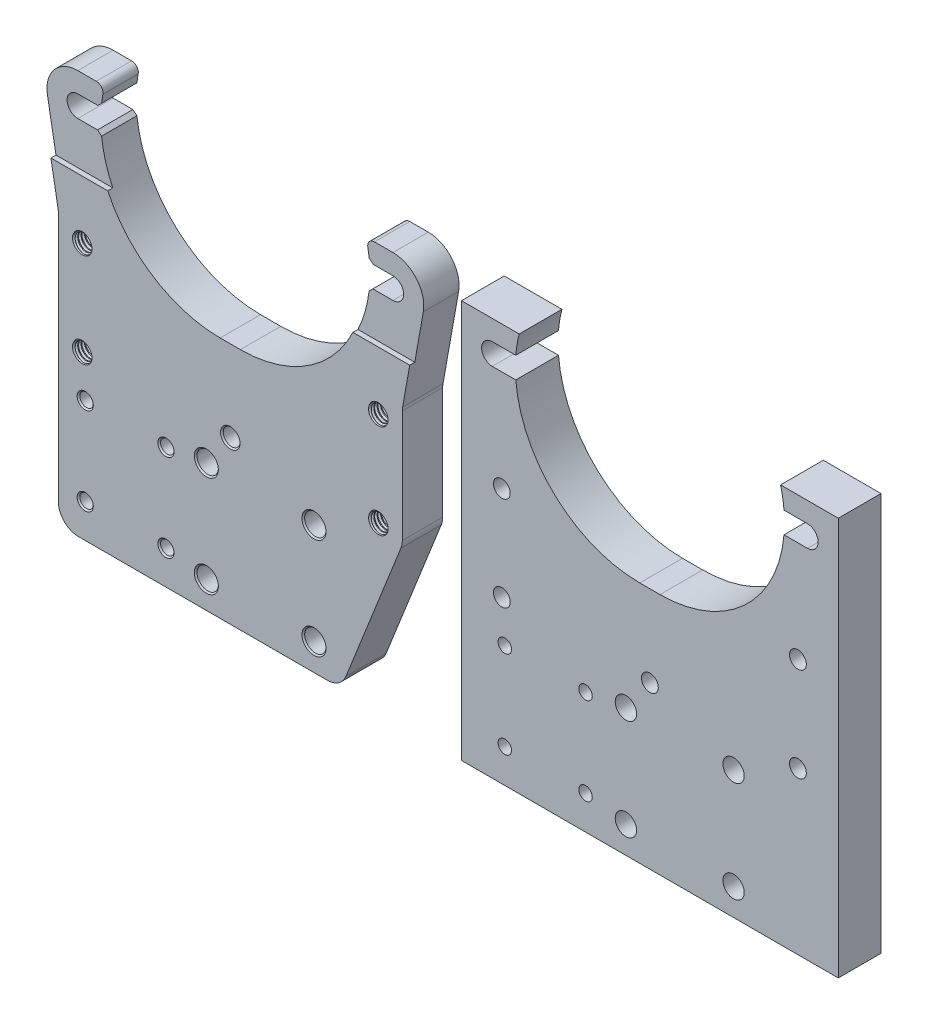
SolidWorks part; units mm, degrees
ref_plane "Front Plane" through (0, 0, 0) normal (0, 0, 1) x (1, 0, 0)
ref_plane "Top Plane" through (0, 0, 0) normal (0, 1, 0) x (1, 0, 0)
ref_plane "Right Plane" through (0, 0, 0) normal (1, 0, 0) x (0, 0, -1)
sketch "Sketch1" plane through (0, 0, 0) normal (0, 0, 1) x (1, 0, 0)
  line L0 (-8, 7.5) -> (8, 7.5) construction
  line L5 (-26, 6.5) -> (-14, 6.5) construction
  line L7 (-8, -7.5) -> (8, -7.5) construction
  line L8 (-8, -7.5) -> (-8, 7.5) construction
  line L9 (-8, 7.5) -> (8, 7.5) construction
  line L10 (8, -7.5) -> (8, 7.5) construction
  line L11 (-8, -7.5) -> (8, 7.5) construction
  line L12 (-8, 7.5) -> (8, -7.5) construction
  line L13 (-8, 7.5) -> (-8, -7.5) construction
  line L14 (-26, -6.5) -> (-14, -6.5) construction
  line L15 (-26, -6.5) -> (-26, 6.5) construction
  line L16 (-26, 6.5) -> (-14, 6.5) construction
  line L17 (-14, -6.5) -> (-14, 6.5) construction
  line L18 (-26, -6.5) -> (-14, 6.5) construction
  line L19 (-26, 6.5) -> (-14, -6.5) construction
  line L20 (0, 0) -> (-20, 0) construction
  line L21 (-6.4375, 59.6343) -> (-6.4375, -58.2445) construction
  line L22 (-30, -11.5) -> (12, -11.5)
  line L23 (-30, -11.5) -> (-30, 11.5)
  line L24 (-30, 11.5) -> (12, 11.5)
  line L25 (12, -11.5) -> (12, 11.5)
  line L26 (-30, -11.5) -> (12, 11.5) construction
  line L27 (-30, 11.5) -> (12, -11.5) construction
  line L28 (-11.5, -15) -> (-28.5, -15) construction
  line L29 (-11.5, -15) -> (-11.5, 15) construction
  line L30 (-11.5, 15) -> (-28.5, 15) construction
  line L31 (-28.5, -15) -> (-28.5, 15) construction
  line L32 (-11.5, -15) -> (-28.5, 15) construction
  line L33 (-11.5, 15) -> (-28.5, -15) construction
  line L34 (-59, 15) -> (41, 15) construction
  line L35 (-59, 15) -> (-59, 24) construction
  line L36 (-59, 24) -> (41, 24) construction
  line L37 (41, 15) -> (41, 24) construction
  line L38 (-59, -10) -> (41, -10) construction
  line L39 (-59, -10) -> (-59, 10) construction
  line L40 (-59, 10) -> (41, 10) construction
  line L41 (41, -10) -> (41, 10) construction
  line L42 (-59, -10) -> (41, 10) construction
  line L43 (-59, 10) -> (41, -10) construction
  line L44 (-30, -11.5) -> (12, -11.5)
  line L45 (-30, -11.5) -> (-30, 29)
  line L46 (-30, 29) -> (12, 29)
  line L47 (12, -11.5) -> (12, 29)
  line L48 (-4.4375, 43.1) -> (17.4825, 43.1) construction
  line L49 (-4.4375, 43.1) -> (-26.3575, 43.1) construction
  line L50 (-24.8575, 43.1) -> (-27.8575, 43.1) construction
  line L51 (-24.8575, 41.5125) -> (-27.8575, 41.5125)
  line L52 (-24.8575, 44.6875) -> (-27.8575, 44.6875)
  line L53 (15.9825, 43.1) -> (18.9825, 43.1) construction
  line L54 (15.9825, 44.6875) -> (18.9825, 44.6875)
  line L55 (15.9825, 41.5125) -> (18.9825, 41.5125)
  line L56 (-24.8575, 44.6875) -> (-22.8693, 44.6875)
  line L57 (-24.8575, 41.5125) -> (-22.8693, 41.5125)
  line L58 (15.9825, 41.5125) -> (13.9943, 41.5125)
  line L59 (15.9825, 44.6875) -> (13.9943, 44.6875)
  line L60 (-4.4375, 43.1) -> (-4.4375, 61.6) construction
  line L61 (12, -11.5) -> (21.125, 11.5)
  line L62 (21.125, 11.5) -> (21.125, 29)
  line L63 (21.125, 29) -> (12, 29)
  line L64 (18.9825, 47.68) -> (14.874, 47.68)
  line L65 (21.125, 29) -> (23.4916, 42.2975)
  line L66 (-30, 29) -> (-32.3666, 42.2975)
  line L67 (-5.9375, 43.1) -> (-2.9375, 43.1) construction
  line L68 (-5.9375, 61.6) -> (-2.9375, 61.6)
  line L69 (-5.9375, 24.6) -> (-2.9375, 24.6)
  line L70 (23.5625, -11.5) -> (13.5725, -7.5366) construction
  line L71 (-32.4375, 47.68) -> (23.5625, 47.68)
  line L72 (-6.4375, 19.5) -> (6.6756, 19.5) construction
  line L73 (-27.8575, 47.68) -> (-23.8616, 47.68)
  line L74 (-32.4375, 47.68) -> (-32.4375, -11.5)
  line L75 (-32.4375, -11.5) -> (23.5625, -11.5)
  line L76 (23.5625, 47.68) -> (23.5625, -11.5)
  circle A0 centre (-8, 7.5) radius 1.5875
  circle A2 centre (8, 7.5) radius 1.5875
  circle A3 centre (8, -7.5) radius 1.5875
  circle A4 centre (-8, -7.5) radius 1.5875
  circle A5 centre (-26, 6.5) radius 1
  circle A6 centre (-14, 6.5) radius 1
  circle A7 centre (-14, -6.5) radius 1
  circle A8 centre (-26, -6.5) radius 1
  circle A9 centre (-8, 7.5) radius 2.9 construction
  circle A10 centre (-14, 6.5) radius 2
  circle A11 centre (-26, 6.5) radius 2
  circle A12 centre (-26, -6.5) radius 2
  circle A13 centre (-14, -6.5) radius 2
  circle A14 centre (-4.4375, 43.1) radius 2 construction
  circle A15 centre (-4.4375, 43.1) radius 8 construction
  circle A16 centre (-4.4375, 43.1) radius 18.5
  circle A17 centre (17.4825, 43.1) radius 1.5875 construction
  circle A18 centre (-26.3575, 43.1) radius 1.5875 construction
  arc A19 (-24.8575, 41.5125) -> (-24.8575, 44.6875) centre (-24.8575, 43.1) ccw
  arc A20 (-27.8575, 44.6875) -> (-27.8575, 41.5125) centre (-27.8575, 43.1) ccw
  arc A21 (15.9825, 44.6875) -> (15.9825, 41.5125) centre (15.9825, 43.1) ccw
  arc A22 (18.9825, 41.5125) -> (18.9825, 44.6875) centre (18.9825, 43.1) ccw
  arc A23 (-5.9375, 61.6) -> (-5.9375, 24.6) centre (-5.9375, 43.1) ccw
  arc A24 (-2.9375, 24.6) -> (-2.9375, 61.6) centre (-2.9375, 43.1) ccw
  circle A25 centre (-26.4375, 26.5) radius 1.25
  circle A26 centre (-26.4375, 12.5) radius 1.25
  circle A29 centre (17.5625, 12.5) radius 1.25
  circle A30 centre (17.5625, 26.5) radius 1.25
  circle A31 centre (-27.8575, 43.1) radius 4.58
  circle A32 centre (18.9825, 43.1) radius 4.58
  circle A33 centre (17.5625, 26.5) radius 2.9 construction
  circle A34 centre (17.5625, 12.5) radius 2.9 construction
  circle A35 centre (-4.4375, 12.5) radius 1.25
  point P0 (0, 0)
  point P1 (-20, 0)
  point P4 (-9, 0)
  point P6 (0, 0)
  point P46 (-9, 15)
  point P47 (-9, 0)
  point P70 (-26.3575, 43.1)
  point P77 (17.4825, 43.1)
  point P97 (-4.4375, 43.1)
  dimension "D5" = 3.175
  dimension "D6" = 2
  dimension "D18" = 5.8
  dimension "D27" = 4
  dimension "D29" = 4
  dimension "D30" = 16
  dimension "D31" = 37
  dimension "D33" = 3.175
  dimension "D35" = 1.5875
  dimension "D40" = 18.5
  dimension "D43" = 2.5
  dimension "D39" = 9.16
  dimension "D48" = 9.16
  dimension "D38" = 5.8
  dimension "D42" = 2.5
  dimension "D1" = 15
  dimension "D2" = 16
  dimension "D3" = 13
  dimension "D4" = 12
  dimension "D9" = 16
  dimension "D10" = 15
  dimension "D13" = 12
  dimension "D14" = 20
  dimension "D15" = 23
  dimension "D16" = 4
  dimension "D17" = 4
  dimension "D19" = 17
  dimension "D20" = 30
  dimension "D21" = 9
  dimension "D22" = 100
  dimension "D23" = 20
  dimension "D24" = 100
  dimension "D25" = 15
  dimension "D26" = 40.5
  dimension "D28" = 13.5625
  dimension "D32" = 21.92
  dimension "D34" = 19.1
  dimension "D36" = 3
  dimension "D37" = 9.125
  dimension "D41" = 3
  dimension "D44" = 20
  dimension "D45" = 4.5
  dimension "D46" = 7
  dimension "D47" = 7
  dimension "D49" = 22
  dimension "D7" = 2
  dimension "D8" = 2
  dimension "D11" = 2
  dimension "D12" = 2
extrude "Boss-Extrude1" add sketch "Sketch1" along normal blind 6 contours A20 L52 L56 A16 L46 L57 L51 | A22 L55 L58 A16 L46 L63 L59 L54 | L62 L63 L47 L25 L61 | A16 L46 L45 L24 L47 | L22 L25 L24 L23 A13 A12 A11 A10 A4 A3 A2 A0 | A10 A6 | A11 A5 | A12 A8 | A13 A7 | A31 L46 A23 | A32 A24 L46 L63 | A31 A23 L73 | A32 L64 A24 region at (-8.6931, -0.0066, 0) region at (15.8976, 13.518, 0) region at (-9.3836, 19.3871, 0) region at (-26.1981, 33.733, 0) region at (-31.0091, 46.2516, 0) region at (17.3231, 33.733, 0) region at (23.4222, 42.708, 0) region at (-24.9644, 47.1601, 0) region at (16.0894, 47.1601, 0) region at (-15.9434, 6.5, 0) region at (-27.9434, 6.5, 0) region at (-27.9434, -6.5, 0) region at (-15.9434, -6.5, 0)
extrude "Cut-Extrude1" cut sketch "Sketch1<3>" along normal blind 2.2 contours A10 A6 | A11 A5 | A12 A8 | A13 A7 | A13 region at (-15.9434, 6.5, 0) region at (-27.9434, 6.5, 0) region at (-27.9434, -6.5, 0) region at (-15.9434, -6.5, 0)
sketch "Sketch1<3>" plane through (0, 0, 0) normal (0, 0, 1) x (1, 0, 0) same geometry as "Sketch1"
chamfer "Chamfer1" distance 0.2 angle 45 26 edges at (-24, 6.5, 0) (-24, -6.5, 0) (-12, -6.5, 0) (-12, 6.5, 0) (-6.4125, -7.5, 0) (9.5875, -7.5, 0) (9.5875, 7.5, 0) (-6.4125, 7.5, 0) (-25, -6.5, 6) (-25, 6.5, 6) (-13, 6.5, 6) (-13, -6.5, 6) (-6.4125, -7.5, 6) (9.5875, -7.5, 6) (9.5875, 7.5, 6) (-6.4125, 7.5, 6) (18.8125, 26.5, 0) (18.8125, 26.5, 6) (18.8125, 12.5, 0) (18.8125, 12.5, 6) (-25.1875, 12.5, 0) (-25.1875, 12.5, 6) (-25.1875, 26.5, 0) (-25.1875, 26.5, 6) (-3.1875, 12.5, 0) (-3.1875, 12.5, 6)
fillet "Fillet1" radius 3 5 edges at (-30, -11.5, 3) (12, -11.5, 3) (21.125, 11.5, 3) (21.125, 29, 3) (-30, 29, 3)
chamfer "Chamfer2" distance 0.5 angle 45 4 edges at (-24.3693, 41.5125, 3) (-24.3693, 44.6875, 3) (15.4943, 44.6875, 3) (15.4943, 41.5125, 3) first distance on face at (-16.7993, 31.2625, 3) first distance on face at (-26.1134, 44.6875, 3) first distance on face at (15.2712, 46.189, 3) first distance on face at (17.2384, 41.5125, 3)
fillet "Fillet4" radius 1 2 edges at (-23.8616, 47.68, 3) (14.9866, 47.68, 3)
thread "Thread1" pitch 0.5 method cut profile "Thread Profile1" start angle 0, offset 1, length 10, pitch 0.5, diameter 2.5
ref_plane "Plane1" through (-27.6875, 26.5, 6.8) normal (0, -1, 0) x (-1, 0, 0)
sketch "Thread Profile1" plane through (-27.6875, 26.5, 6.8) normal (0, -1, 0) x (-1, 0, 0)
  line L0 (0, 0) -> (0, 0.5) construction
  line L1 (0, 0) -> (0.2706, 0.1562)
  line L2 (0.2706, 0.1562) -> (0.2706, 0.2187)
  line L3 (0.2706, 0.2187) -> (0, 0.375)
  line L4 (0.2706, 0.1875) -> (0, 0.1875) construction
  line L11 (0, 0) -> (0, 0.375)
  point P2 (0, 0)
  dimension "Pitch" = 0.5
  dimension "Profile_Angle" = 60
  dimension "Profile_Land" = 0.0625
  dimension "Profile_Height" = 0.2706
pattern_linear "LPattern1" count 2 spacing 44 along (1, 0, 0) count 2 spacing 14 along (0, -1, 0) of "Thread1"
extrude "Boss-Extrude3" add sketch "Sketch1<5>" along normal blind 6.35 separate body contours L23 L45 | A23 L46 L57 L51 A20 L52 L56 | A26 L24 L47 L46 A24 L69 A23 L45 A25 | A26 L24 L23 L22 L25 A13 A12 A11 A10 A4 A3 A2 A0 | L62 L63 L47 L25 L61 A29 A30 | L62 L61 | A24 L59 L54 A22 L55 L58 L46 L63 | A10 A6 | A11 A5 | A12 A8 | A13 A7 | A31 L66 L46 A23 | A32 A24 L46 L63 L65 | A31 L71 L74 | A31 A23 L71 | A32 L76 L71 | A32 L64 A24 region at (-8.6931, -0.0066, 0) region at (-31.2776, 12.3402, 0) region at (15.8976, 13.518, 0) region at (20.3456, 4.638, 0) region at (-9.3836, 19.3871, 0) region at (-26.1981, 33.733, 0) region at (-31.4145, 46.657, 0) region at (-31.0091, 46.2516, 0) region at (17.3231, 33.733, 0) region at (22.5395, 46.657, 0) region at (23.4222, 42.708, 0) region at (-24.9644, 47.1601, 0) region at (16.0894, 47.1601, 0) region at (-15.9434, 6.5, 0) region at (-27.9434, 6.5, 0) region at (-27.9434, -6.5, 0) region at (-15.9434, -6.5, 0)
sketch "Sketch1<5>" plane through (0, 0, 0) normal (0, 0, 1) x (1, 0, 0) same geometry as "Sketch1"
extrude "Cut-Extrude2" cut sketch "Sketch1<7>" along normal blind 2.2 contours A10 A6 | A11 A5 | A12 A8 | A13 A7 region at (-15.9434, 6.5, 0) region at (-27.9434, 6.5, 0) region at (-27.9434, -6.5, 0) region at (-15.9434, -6.5, 0)
sketch "Sketch1<7>" plane through (0, 0, 0) normal (0, 0, 1) x (1, 0, 0) same geometry as "Sketch1"
move or copy body "Body-Move/Copy1" bodies to move or copy 109 copy no translate (62.7049, 0, 0)
sketch "Sketch2" plane through (0, 0, 0) normal (0, 0, -1) x (-1, 0, 0)
  line L0 (27.8575, 47.68) -> (25.1061, 47.68) construction
  line L1 (-36.3719, 47.68) -> (43.0334, 47.68)
  line L2 (-36.3719, 47.68) -> (-36.3719, 35.18)
  line L3 (-36.3719, 35.18) -> (43.0334, 35.18)
  line L4 (43.0334, 47.68) -> (43.0334, 35.18)
  dimension "D1" = 12.5
extrude "Cut-Extrude3" cut sketch "Sketch2" along normal blind 0.75 from surface starting at face at (-2.9875, 12.5, 6)
